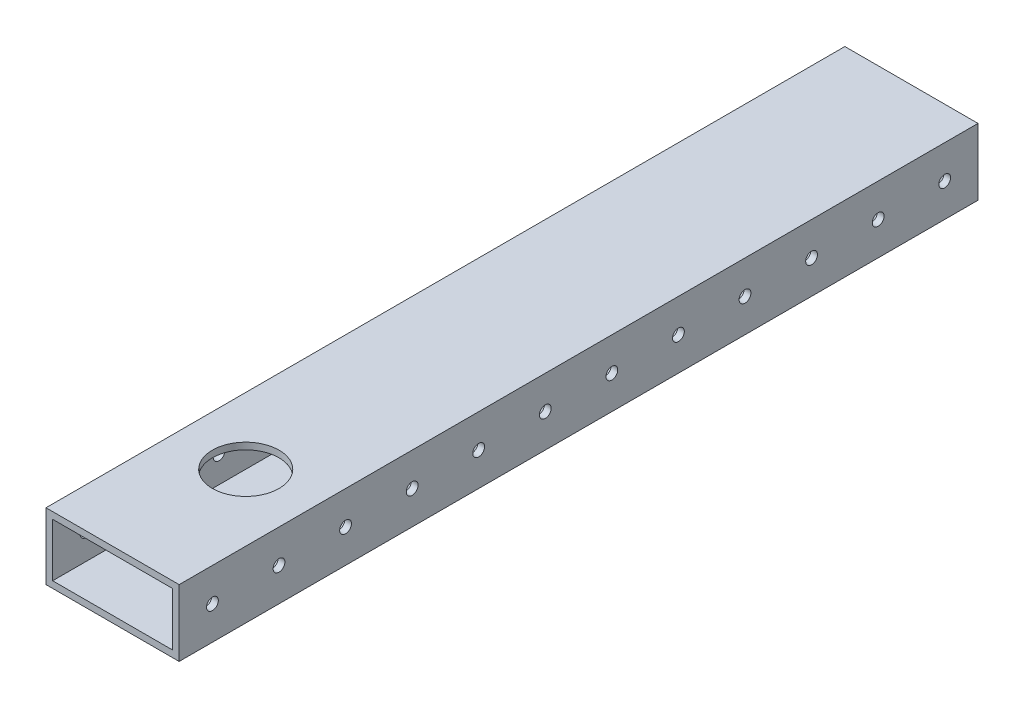
SolidWorks part; units mm, degrees
ref_plane "Front Plane" through (0, 0, 0) normal (0, 0, 1) x (1, 0, 0)
ref_plane "Top Plane" through (0, 0, 0) normal (0, 1, 0) x (1, 0, 0)
ref_plane "Right Plane" through (0, 0, 0) normal (1, 0, 0) x (0, 0, -1)
sketch "Sketch1" plane through (0, 0, 0) normal (0, 0, 1) x (1, 0, 0)
  line L1 (-25.4, -12.7) -> (25.4, -12.7)
  line L2 (-25.4, -12.7) -> (-25.4, 12.7)
  line L3 (-25.4, 12.7) -> (25.4, 12.7)
  line L4 (25.4, -12.7) -> (25.4, 12.7)
  line L5 (-25.4, -12.7) -> (25.4, 12.7) construction
  line L6 (-25.4, 12.7) -> (25.4, -12.7) construction
  line L7 (-22.86, -10.16) -> (22.86, -10.16)
  line L8 (-22.86, -10.16) -> (-22.86, 10.16)
  line L9 (-22.86, 10.16) -> (22.86, 10.16)
  line L10 (22.86, -10.16) -> (22.86, 10.16)
  line L11 (-22.86, -10.16) -> (22.86, 10.16) construction
  line L12 (-22.86, 10.16) -> (22.86, -10.16) construction
  point P0 (0, 0)
  point P6 (0, 0)
  dimension "D1" = 50.8
  dimension "D2" = 25.4
  dimension "D3" = 2.54
  dimension "D4" = 2.54
extrude "Boss-Extrude1" add sketch "Sketch1" against normal blind 355.6
hole_wizard "#8 Clearance Hole1" positions "Sketch2" profile "Sketch3" hole size "#8" standard "ANSI Inch" end condition through all
sketch "Sketch2" plane through (25.4, 0, 0) normal (1, 0, 0) x (0, 0, -1)
  line L0 (355.6, -12.7) -> (0, -12.7) construction
  point P0 (12.7, 0)
  point P16 (38.1, 0)
  point P17 (63.5, 0)
  point P18 (88.9, 0)
  point P19 (114.3, 0)
  point P20 (139.7, 0)
  point P21 (165.1, 0)
  point P22 (190.5, 0)
  point P23 (215.9, 0)
  point P24 (241.3, 0)
  point P25 (266.7, 0)
  point P26 (292.1, 0)
  point P27 (317.5, 0)
  point P28 (342.9, 0)
  dimension "D1" = 12.7
  dimension "D2" = 12.7
  dimension "D3" = 14
sketch "Sketch3" plane through (25.4, 0, -12.7) normal (0, 1, 0) x (0, 0, -1)
  line L0 (0, 0) -> (0, 50.8)
  line L1 (0, 50.8) -> (2.2479, 50.8)
  line L2 (2.2479, 50.8) -> (2.2479, 0)
  line L5 (2.2479, 0) -> (0, 0)
  line L11 (0, -6.35) -> (0, 107.95) construction
  dimension "Thru Hole Dia." = 4.4958
  dimension "Thru Hole Depth" = 50.8
hole_wizard "1 (1) Diameter Hole1" positions "Sketch6" profile "Sketch7" hole size "1" standard "ANSI Inch" end condition through all
sketch "Sketch6" plane through (0, 12.7, 0) normal (0, 1, 0) x (1, 0, 0)
  line L0 (25.4, 355.6) -> (25.4, 0) construction
  line L1 (25.4, 0) -> (-25.4, 0) construction
  point P0 (0, 101.6)
  dimension "D1" = 25.4
  dimension "D2" = 101.6
sketch "Sketch7" plane through (0, 12.7, -101.6) normal (1, 0, 0) x (0, 0, 1)
  line L0 (0, 0) -> (0, 25.4)
  line L1 (0, 25.4) -> (12.7, 25.4)
  line L2 (12.7, 25.4) -> (12.7, 0)
  line L5 (12.7, 0) -> (0, 0)
  line L11 (0, -6.35) -> (0, 107.95) construction
  dimension "Thru Hole Dia." = 25.4
  dimension "Thru Hole Depth" = 25.4
sketch "Sketch8" plane through (0, 12.7, 0) normal (0, 1, 0) x (1, 0, 0)
  line L0 (25.4, 0) -> (25.4, 50.8)
  line L1 (25.4, 355.6) -> (25.4, 0) construction
  line L2 (25.4, 50.8) -> (60.3179, 50.8)
  line L3 (60.3179, 50.8) -> (60.3179, -5.2193)
  line L4 (60.3179, -5.2193) -> (-35.9606, -5.2193)
  line L5 (-35.9606, -5.2193) -> (-35.9606, 50.8)
  line L6 (-35.9606, 50.8) -> (25.4, 50.8)
  line M3 (-25.4, 0) -> (25.4, 0)
  line M4 (25.4, 0) -> (25.4, 355.6)
  line M6 (-25.4, 355.6) -> (-25.4, 0)
  dimension "D1" = 50.8
extrude "Cut-Extrude1" cut sketch "Sketch8" against normal blind 71.882 and the other way blind 421.64 contours L6 M6 M3 M4 region at (0, 12.7, -25.4)
